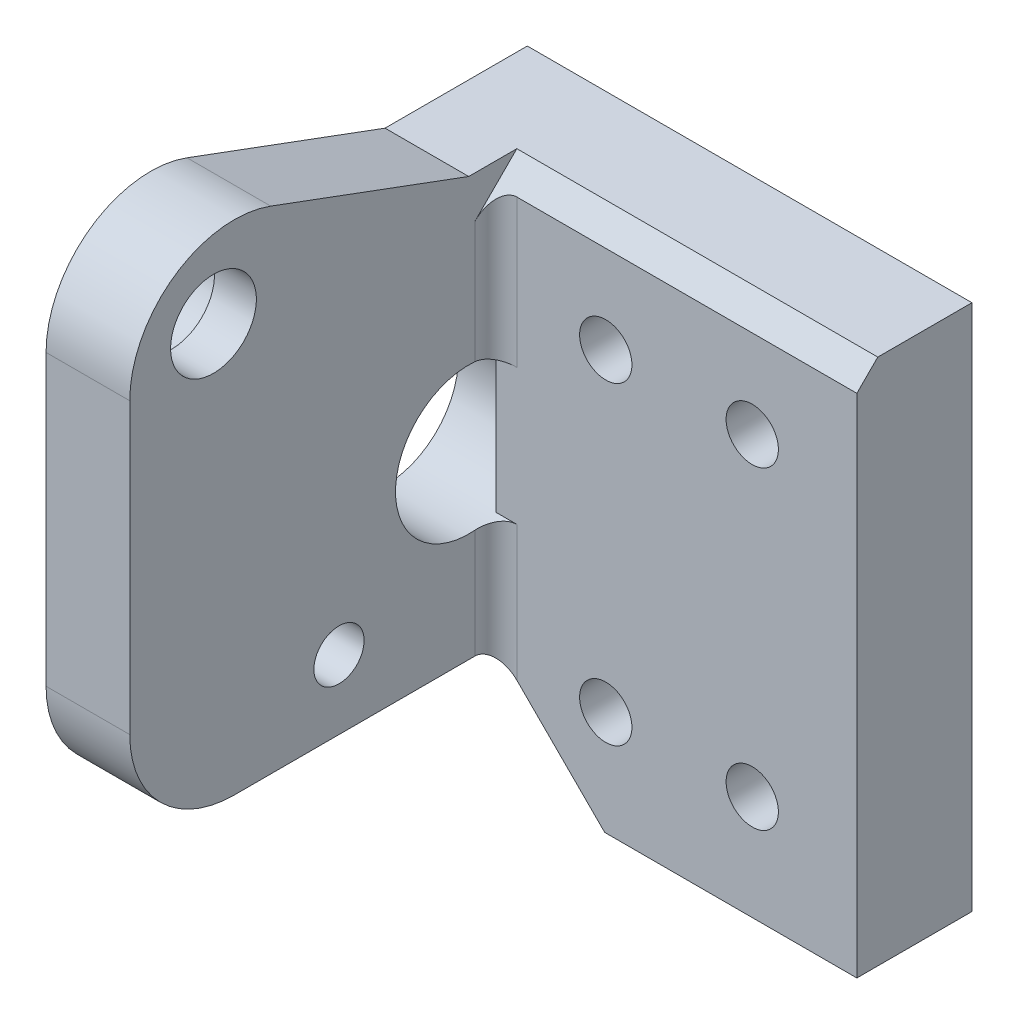
SolidWorks part; units mm, degrees
material "7075-T6，板材(SS)"
ref_plane "前视基准面" through (0, 0, 0) normal (0, 0, 1) x (1, 0, 0)
ref_plane "上视基准面" through (0, 0, 0) normal (0, 1, 0) x (1, 0, 0)
ref_plane "右视基准面" through (0, 0, 0) normal (1, 0, 0) x (0, 0, -1)
sketch "草图1" plane through (0, 0, 0) normal (0, 0, 1) x (1, 0, 0)
  line L0 (0, 12) -> (0, -12) construction
  line L1 (-34.75, 12) -> (34.75, 12)
  line L2 (-34.75, 12) -> (-34.75, -12)
  line L3 (-34.75, -12) -> (34.75, -12)
  line L4 (34.75, 12) -> (34.75, -12)
  dimension "D1" = 24
  dimension "D2" = 69.5
extrude "拉伸1" add sketch "草图1" along normal blind 10.5
sketch "草图2" plane through (0, -12, 0) normal (0, -1, 0) x (1, 0, 0)
  line L0 (-34.75, 0) -> (34.75, 0) construction
  line L1 (-17.5, 0) -> (17.5, 0)
  line L2 (-17.5, 0) -> (-17.5, 3)
  line L3 (-17.5, 3) -> (17.5, 3)
  line L4 (17.5, 0) -> (17.5, 3)
  line L5 (0, 0) -> (0, 3) construction
  dimension "D1" = 3
  dimension "D2" = 35
extrude "拉伸2" cut sketch "草图2" against normal up to surface (24 mm away) up to face at (0, 12, 5.25)
sketch "草图3" plane through (0, 0, 0) normal (0, 0, -1) x (-1, 0, 0)
  line L0 (0, 8) -> (0, -7) construction
  line L1 (-22.5, 8) -> (22.5, 8)
  line L2 (-22.5, 8) -> (-22.5, -7)
  line L3 (-22.5, -7) -> (22.5, -7)
  line L4 (22.5, 8) -> (22.5, -7)
  line L5 (17.5, 12) -> (-17.5, 12) construction
  point P8 (-29.5, 8)
  point P10 (-29.5, -7)
  point P11 (29.5, -7)
  point P12 (29.5, 8)
  dimension "D1" = 45
  dimension "D2" = 15
  dimension "D3" = 4
  dimension "D4" = 7
  dimension "D5" = 7
  dimension "D6" = 7
  dimension "D7" = 7
hole_wizard "M3 螺纹孔1" positions "3D草图1" profile "草图4" tap size "M3" standard "GB"
sketch3d "3D草图1"
  point P0 (22.5, 8, 0)
  point P3 (22.5, -7, 0)
  point P6 (-22.5, -7, 0)
  point P9 (-22.5, 8, 0)
  point P12 (29.5, 8, 0)
  point P15 (29.5, -7, 0)
  point P18 (-29.5, -7, 0)
  point P21 (-29.5, 8, 0)
cosmetic thread "孔螺蚊线1" parameters "D1"=5.5, "D2"=3
cosmetic thread "孔螺蚊线2" parameters "D1"=5.5, "D2"=3
cosmetic thread "孔螺蚊线3" parameters "D1"=5.5, "D2"=3
cosmetic thread "孔螺蚊线4" parameters "D1"=5.5, "D2"=3
cosmetic thread "Cosmetic Thread1" parameters "D1"=6, "D2"=3
cosmetic thread "Cosmetic Thread2" parameters "D1"=6, "D2"=3
cosmetic thread "Cosmetic Thread3" parameters "D1"=6, "D2"=3
cosmetic thread "Cosmetic Thread4" parameters "D1"=6, "D2"=3
sketch "草图4" plane through (22.5, 8, 0) normal (1, 0, 0) x (0, 1, 0)
  line L0 (0, 0) -> (0, 8.2511)
  line L1 (0, 8.2511) -> (1.25, 7.5)
  line L2 (1.25, 7.5) -> (1.25, 0)
  line L5 (1.25, 0) -> (0, 0)
  line L10 (0, 8.2511) -> (-1.25, 7.5) construction
  line L11 (0, -6.35) -> (0, 107.95) construction
  dimension "螺纹孔钻头直径" = 2.5
  dimension "螺纹孔钻头深度" = 7.5
  dimension "导头角度" = 118
chamfer "倒角1" distance 0.5 angle 45 4 edges at (-23.75, 8, 0) (-23.75, -7, 0) (21.25, -7, 0) (21.25, 8, 0)
chamfer "倒角2" distance 0.5 angle 45 4 edges at (-30.75, -7, 0) (-30.75, 8, 0) (28.25, -7, 0) (28.25, 8, 0)
chamfer "倒角3" distance 5.2 angle 45 2 edges at (-34.75, -12, 5.25) (34.75, -12, 5.25)
sketch "草图5" plane through (34.75, 0, 0) normal (1, 0, 0) x (0, 0, -1)
  line L0 (-3, 12) -> (-3, 8.25)
  line L1 (-10.5, 12) -> (0, 12) construction
  line L2 (-3, 8.25) -> (-3, -2.75)
  line L3 (0, -6.8) -> (0, 12) construction
  dimension "D1" = 11
  dimension "D2" = 3.75
  dimension "D3" = 3
fillet "Fillet1" radius 2 1 edges at (0, -12, 10.5)
sketch "草图7" plane through (0, 0, 10.5) normal (0, 0, 1) x (1, 0, 0)
  line L0 (29.55, -12) -> (-29.55, -12) construction
  line L1 (-17.5, 18) -> (17.5, 18)
  line L2 (-17.5, 18) -> (-17.5, -12)
  line L3 (-17.5, -12) -> (17.5, -12)
  line L4 (17.5, 18) -> (17.5, -12)
  dimension "D1" = 30
  dimension "D2" = 35
  dimension "D3" = 17.5
sketch "草图8" plane through (34.75, 0, 0) normal (1, 0, 0) x (0, 0, -1)
  line L0 (0, -6.8) -> (0, 12) construction
  line L1 (-10.5, 12) -> (0, 12)
  line L2 (-10.5, 12) -> (-10.5, 13.2)
  line L3 (-10.5, 13.2) -> (0, 13.2)
  line L4 (0, 12) -> (0, 13.2)
  dimension "D1" = 1.2
extrude "凸台-拉伸1" add sketch "草图8" against normal blind 69.5 contours L3 L4 L1 L2
extrude "切除-拉伸1" cut sketch "草图7" against normal blind 71.5
chamfer "倒角6" [suppressed] distance 1.5 angle 55
chamfer "倒角7" [suppressed] distance 1.5 angle 55
fillet "圆角1" radius 2 1 edges at (26.125, 13.2, 10.5)
fillet "圆角2" radius 2 1 edges at (-26.125, 13.2, 10.5)
sketch "Sketch2" plane through (0, 0, 10.5) normal (0, 0, 1) x (1, 0, 0)
  line L1 (42.2661, -18.1364) -> (26, -18.1364)
  line L2 (42.2661, -18.1364) -> (42.2661, 17.6642)
  line L3 (42.2661, 17.6642) -> (26, 17.6642)
  line L4 (26, -18.1364) -> (26, 17.6642)
  line L5 (-26, -17.3003) -> (-42.7222, -17.3003)
  line L6 (-26, -17.3003) -> (-26, 21.0087)
  line L7 (-26, 21.0087) -> (-42.7222, 21.0087)
  line L8 (-42.7222, -17.3003) -> (-42.7222, 21.0087)
  dimension "D1" = 26
  dimension "D2" = 26
extrude "Extrude1" cut sketch "Sketch2" against normal blind 5
sketch "Sketch4" plane through (-34.75, 0, 0) normal (-1, 0, 0) x (0, 0, 1)
  line L0 (0, -6.8) -> (0, 13.2)
  line L1 (0, 13.2) -> (6.8, 13.2)
  line L2 (6.8, 13.2) -> (23, 19.2)
  line L3 (23, -6.8) -> (23, 19.2)
  line L4 (23, -6.8) -> (0, -6.8)
  circle A0 centre (19, 13.2) radius 2.05
  circle A1 centre (6.8, 1.9) radius 3.5
  dimension "D7" = 4.1
  dimension "D9" = 7
  dimension "D1" = 20
  dimension "D2" = 23
  dimension "D3" = 6.8
  dimension "D4" = 26
  dimension "D5" = 20
  dimension "D6" = 19
  dimension "D8" = 6.8
  dimension "D10" = 8.7
extrude "Extrude2" add sketch "Sketch4" along normal blind 4
fillet "Fillet2" radius 5 2 edges at (-36.75, -6.8, 23) (-36.75, 19.2, 23)
sketch "Sketch5" plane through (-38.75, 0, 0) normal (-1, 0, 0) x (0, 0, 1)
  line L0 (0, -6.8) -> (18, -6.8) construction
  line L1 (0, 13.2) -> (0, -6.8) construction
  point P0 (13, -3.5)
  dimension "D1" = 3.3
  dimension "D2" = 13
sketch "Sketch7" plane through (34.75, 0, 0) normal (1, 0, 0) x (0, 0, -1)
  line L0 (0, -6.798) -> (0, 13.202)
  line L5 (-23, -6.798) -> (0, -6.798)
  line L6 (-23, 19.202) -> (-23, -6.798)
  line L7 (-6.8, 13.202) -> (-23, 19.202)
  line L8 (0, 13.202) -> (-6.8, 13.202)
  circle A2 centre (-6.8, 1.9) radius 3.5
  circle A3 centre (-19, 13.2) radius 2.05
  point P2 (0, 13.2)
  dimension "D1" = 20
  dimension "D2" = 23
  dimension "D3" = 26
  dimension "D4" = 6.8
extrude "Extrude3" add sketch "Sketch7" along normal blind 4
fillet "Fillet3" radius 5 2 edges at (36.75, 19.202, 23) (36.75, -6.798, 23)
sketch "Sketch9" plane through (38.75, 0, 0) normal (1, 0, 0) x (0, 0, -1)
  point P0 (-13, -3.5)
hole_wizard "CSK for M2 Slotted raised CTSK head wood screws2" positions "3DSketch5" profile "Sketch12" countersink size "M2" standard "GB" end condition up to next
sketch3d "3DSketch5"
  point P0 (38.75, -3.5, 13)
sketch "Sketch12" plane through (38.75, -3.5, 13) normal (0, 1, 0) x (0, 0, -1)
  line L0 (0, 0) -> (0, 77.5)
  line L1 (0, 77.5) -> (1.2, 77.5)
  line L2 (1.2, 77.5) -> (1.2, 1.05)
  line L3 (1.2, 1.05) -> (2.25, 0)
  line L5 (2.25, 0) -> (0, 0)
  line L6 (-1.2, 1.05) -> (-2.25, 0) construction
  line L11 (0, -6.35) -> (0, 107.95) construction
  dimension "通孔孔直径" = 2.4
  dimension "通孔孔深度" = 77.5
  dimension "近端锥形沉头孔直径" = 4.5
  dimension "近端锥形沉头孔角度" = 90
hole_wizard "CSK for M2 Slotted raised CTSK head wood screws3" positions "3DSketch6" profile "Sketch13" countersink size "M2" standard "GB" end condition up to next
sketch3d "3DSketch6"
  point P0 (-38.75, -3.5, 13)
sketch "Sketch13" plane through (-38.75, -3.5, 13) normal (0, 1, 0) x (0, 0, 1)
  line L0 (0, 0) -> (0, 4)
  line L1 (0, 4) -> (1.2, 4)
  line L2 (1.2, 4) -> (1.2, 1.05)
  line L3 (1.2, 1.05) -> (2.25, 0)
  line L5 (2.25, 0) -> (0, 0)
  line L6 (-1.2, 1.05) -> (-2.25, 0) construction
  line L11 (0, -6.35) -> (0, 107.95) construction
  dimension "通孔孔直径" = 2.4
  dimension "通孔孔深度" = 4
  dimension "近端锥形沉头孔直径" = 4.5
  dimension "近端锥形沉头孔角度" = 90
fillet "Fillet5" radius 1 3 edges at (34.75, -4.0738, 5.5) (34.75, 9.1748, 5.5) (26, 0.6, 5.5)
sketch "Sketch14" plane through (-38.75, 0, 0) normal (-1, 0, 0) x (0, 0, 1)
  circle A0 centre (19, 13.2) radius 2.4
  dimension "D1" = 4.8
extrude "Extrude4" cut sketch "Sketch14" against normal blind 2
sketch "Sketch15" plane through (38.75, 0, 0) normal (1, 0, 0) x (0, 0, -1)
  circle A0 centre (-19, 13.2) radius 2.4
  dimension "D1" = 4.8
extrude "Extrude5" cut sketch "Sketch15" against normal blind 2
sketch "草图9" plane through (0, 0, 23) normal (0, 0, 1) x (1, 0, 0)
  line L1 (3.4911, 22.96) -> (40.142, 22.96)
  line L2 (3.4911, 22.96) -> (3.4911, -24.6532)
  line L3 (3.4911, -24.6532) -> (40.142, -24.6532)
  line L4 (40.142, 22.96) -> (40.142, -24.6532)
extrude "切除-拉伸2" cut sketch "草图9" against normal through all
sketch "草图10" plane through (0, 0, 10.5) normal (0, 0, 1) x (1, 0, 0)
  line L1 (-28.6011, 21.6333) -> (-11.8736, 21.6333)
  line L2 (-28.6011, 21.6333) -> (-28.6011, -17.7322)
  line L3 (-28.6011, -17.7322) -> (-11.8736, -17.7322)
  line L4 (-11.8736, 21.6333) -> (-11.8736, -17.7322)
extrude "切除-拉伸3" cut sketch "草图10" against normal up to surface (5 mm away) up to face at (-31.5071, -0.0857, 5.5)
chamfer "倒角8" distance 1 angle 45 1 edges at (-26.125, 13.2, 5.5)
fillet "圆角4" radius 1 2 edges at (-34.75, 8.6748, 5.5) (-34.75, -4.0748, 5.5)
